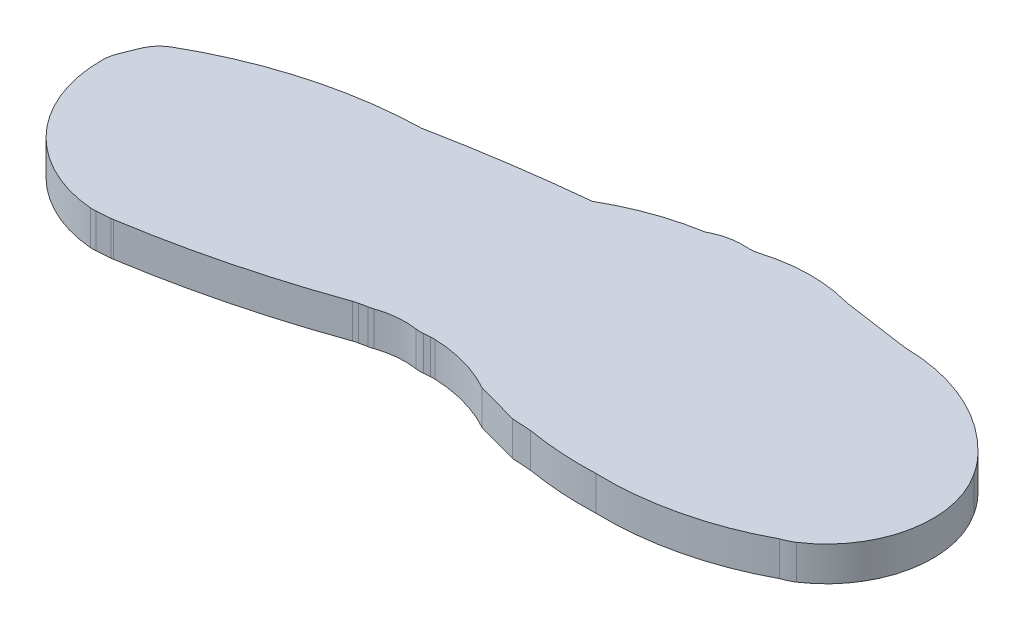
SolidWorks part; units mm, degrees
ref_plane "Front Plane" through (0, 0, 0) normal (0, 0, 1) x (1, 0, 0)
ref_plane "Top Plane" through (0, 0, 0) normal (0, 1, 0) x (1, 0, 0)
ref_plane "Right Plane" through (0, 0, 0) normal (1, 0, 0) x (0, 0, -1)
sketch "Sketch1" plane through (0, 0, 0) normal (0, 1, 0) x (1, 0, 0)
  line L0 (45.8333, 91.5) -> (229.1667, 91.5) construction
  line L9 (51.8053, 46.2547) -> (56.8676, 46.6901)
  line L12 (79.0038, 114.3802) -> (83.0543, 114.7286)
  line L14 (55.8689, 56.4332) -> (15.5662, 87.3281)
  line L15 (59.6317, 65.8579) -> (19.3289, 96.7529)
  line L16 (15.5662, 87.3281) -> (19.3289, 96.7529)
  line L19 (69.8952, 80.3749) -> (117.3677, 118.5887)
  line L21 (133.3146, 63.2727) -> (129.5681, 62.9505)
  line L23 (129.5681, 62.9505) -> (105.0351, 105.8988)
  line L25 (116.8247, 61.8545) -> (113.0574, 61.1029)
  line L26 (116.8247, 61.8545) -> (90.8367, 92.1886)
  line L27 (113.0574, 61.1029) -> (87.0695, 91.437)
  line L29 (184.4471, 132.2095) -> (204.3821, 129.3605)
  line L33 (165.1854, 54.5779) -> (153.0409, 57.8911)
  line L39 (160.5906, 102.174) -> (179.6581, 104.9064)
  line L43 (197.9816, 92.87) -> (234.0782, 63.123)
  line L46 (219.8398, 79.2449) -> (240.395, 112.1443)
  line L47 (225.5366, 74.5502) -> (246.0919, 107.4496)
  line L50 (119.3858, 87.3281) -> (144.8138, 109.1257)
  line L51 (123.3576, 80.3749) -> (148.7857, 102.1725)
  line L53 (144.8138, 109.1257) -> (147.8433, 111.9787)
  line L54 (108.6025, 106.2056) -> (107.5216, 107.9003)
  line L55 (107.5216, 107.9003) -> (115.1407, 114.0334)
  line L56 (105.0351, 105.8988) -> (90.8367, 92.1886)
  line L57 (87.0695, 91.437) -> (66.5995, 71.8536)
  line L58 (56.8676, 46.6901) -> (66.5995, 71.8536)
  line L59 (69.8952, 80.3749) -> (83.0543, 114.7286)
  line L60 (55.8689, 56.4332) -> (51.8053, 46.2547)
  line L61 (59.6317, 65.8579) -> (79.0038, 114.3802)
  line L62 (115.1407, 114.0334) -> (122.5537, 120.4385)
  line L63 (108.6025, 106.2056) -> (119.3858, 87.3281)
  line L64 (123.3576, 80.3749) -> (133.3146, 63.2727)
  line L65 (148.7857, 102.1725) -> (153.0409, 57.8911)
  line L66 (147.8433, 111.9787) -> (146.1657, 129.4371)
  line L67 (158.3087, 125.8107) -> (157.7665, 131.4276)
  line L68 (160.0972, 107.2851) -> (180.4194, 109.247)
  line L69 (158.3087, 125.8107) -> (160.0972, 107.2851)
  line L70 (160.5906, 102.174) -> (165.1854, 54.5779)
  line L71 (180.4194, 109.247) -> (184.4471, 132.2095)
  line L72 (179.6581, 104.9064) -> (170.7675, 54.2189)
  line L73 (190.9742, 52.9192) -> (197.9816, 92.87)
  line L74 (198.6541, 96.7039) -> (204.3821, 129.3605)
  line L75 (198.6541, 96.7039) -> (219.8398, 79.2449)
  line L76 (225.5366, 74.5502) -> (237.4451, 64.7364)
  line L78 (240.395, 112.1443) -> (241.2539, 113.519)
  line L79 (117.3677, 118.5887) -> (122.0886, 120.7766)
  arc A5 (241.2539, 113.519) -> (246.0919, 107.4496) centre (216.3148, 88.677) cw
  arc A6 (237.4451, 64.7364) -> (234.0782, 63.123) centre (229.0743, 77.8855) cw
  arc A7 (170.7675, 54.2189) -> (190.9742, 52.9192) centre (187.1326, 150.9211) ccw
  arc A8 (146.1657, 129.4371) -> (157.7665, 131.4276) centre (154.881, 113.4441) cw
  arc A9 (122.0886, 120.7766) -> (122.5537, 120.4385) centre (122.1521, 120.375) cw
extrude "Boss-Extrude1" add sketch "Sketch1" along normal blind 10
sketch "Sketch3" plane through (0, 0, 0) normal (0, -1, 0) x (-1, 0, 0)
  line L0 (-184.4471, 132.2095) -> (-184.0963, 130.2095)
  line L1 (-184.4471, 132.2095) -> (-180.4194, 109.247) construction
  line L2 (-157.7665, 131.4276) -> (-157.9596, 129.4276)
  line L3 (-160.0972, 107.2851) -> (-157.7665, 131.4276) construction
  arc A0 (-184.4471, 132.2095) -> (-157.7665, 131.4276) centre (-172.3516, 89.3377) cw
  arc A1 (-184.0963, 130.2095) -> (-157.9596, 129.4276) centre (-172.3013, 87.2492) cw
  dimension "D3" = 44.5453
  dimension "D4" = 44.55
  dimension "D1" = 2
  dimension "D2" = 2
extrude "Boss-Extrude2" add sketch "Sketch3" against normal blind 10
fillet "Fillet1" radius 10 1 edges at (157.7665, 5, -131.4276)
sketch "Sketch4" plane through (0, 0, 0) normal (0, -1, 0) x (1, 0, 0)
  line L0 (241.2539, -113.519) -> (240.1941, -111.8228)
  line L1 (241.2539, -113.519) -> (219.8398, -79.2449) construction
  line L2 (204.3821, -129.3605) -> (204.0366, -127.3905)
  line L3 (198.6541, -96.7039) -> (204.3821, -129.3605) construction
  arc A0 (241.2539, -113.519) -> (204.3821, -129.3605) centre (203.881, -77.3629) cw
  arc A1 (240.1941, -111.8228) -> (204.0366, -127.3905) centre (203.0818, -75.3993) cw
  dimension "D1" = 52
  dimension "D4" = 52
  dimension "D2" = 2
  dimension "D3" = 2
extrude "Boss-Extrude3" add sketch "Sketch4" against normal blind 10
fillet "Fillet2" radius 10 1 edges at (204.3821, 5, -129.3605)
fillet "Fillet3" radius 10 1 edges at (184.4471, 5, -132.2095)
sketch "Sketch5" plane through (0, 0, 0) normal (0, -1, 0) x (-1, 0, 0)
  line L0 (-146.1657, 129.4371) -> (-146.357, 127.4462)
  line L1 (-146.1657, 129.4371) -> (-147.8433, 111.9787) construction
  arc A0 (-122.0886, 120.7766) -> (-146.1657, 129.4371) centre (-158.297, 57.9116) ccw
  arc A1 (-122.0886, 120.7766) -> (-122.5537, 120.4385) centre (-122.1521, 120.375) ccw
  arc A2 (-146.357, 127.4462) -> (-122.5537, 120.4385) centre (-154.6429, 55.3709) cw
  dimension "D1" = 72.5469
  dimension "D3" = 72.55
  dimension "D2" = 2
extrude "Boss-Extrude4" add sketch "Sketch5" against normal blind 10
sketch "Sketch6" plane through (0, 0, 0) normal (0, -1, 0) x (1, 0, 0)
  line L0 (117.3677, -118.5887) -> (83.0543, -114.7286)
  line L1 (83.0543, -114.7286) -> (79.0038, -114.3802)
  line L2 (122.0886, -120.7766) -> (117.3677, -118.5887)
  arc A0 (122.0886, -120.7766) -> (79.0038, -114.3802) centre (166.68, 327.8872) cw
extrude "Boss-Extrude5" add sketch "Sketch6" against normal blind 10
sketch "Sketch7" plane through (0, 10, 0) normal (0, 1, 0) x (1, 0, 0)
  line L0 (79.0038, 114.3802) -> (78.2622, 112.5228)
  line L1 (79.0038, 114.3802) -> (59.6317, 65.8579) construction
  line L2 (19.3289, 96.7529) -> (20.9162, 95.5361)
  line L3 (59.6317, 65.8579) -> (19.3289, 96.7529) construction
  arc A0 (79.0038, 114.3802) -> (19.3289, 96.7529) centre (81.9672, -5.4758) ccw
  arc A1 (20.9162, 95.5361) -> (78.2622, 112.5228) centre (82.5636, -7.29) cw
  dimension "D2" = 119.8927
  dimension "D4" = 119.89
  dimension "D1" = 2
  dimension "D3" = 2
extrude "Boss-Extrude6" add sketch "Sketch7" against normal blind 10
sketch "Sketch8" plane through (0, 0, 0) normal (0, -1, 0) x (1, 0, 0)
  line L0 (51.8053, -46.2547) -> (52.5468, -48.1122)
  line L1 (55.8689, -56.4332) -> (51.8053, -46.2547) construction
  line L2 (15.5662, -87.3281) -> (17.1535, -86.1114)
  line L3 (15.5662, -87.3281) -> (55.8689, -56.4332) construction
  arc A0 (15.5662, -87.3281) -> (51.8053, -46.2547) centre (54.2224, -84.911) cw
  arc A1 (17.1535, -86.1114) -> (52.5468, -48.1122) centre (55.879, -86.6986) cw
  dimension "D2" = 38.7317
  dimension "D4" = 38.73
  dimension "D1" = 2
  dimension "D3" = 2
extrude "Boss-Extrude7" add sketch "Sketch8" against normal blind 10
sketch "Sketch9" plane through (0, 0, 0) normal (0, -1, 0) x (1, 0, 0)
  line L0 (56.8676, -46.6901) -> (57.589, -48.5554)
  line L1 (56.8676, -46.6901) -> (66.5995, -71.8536) construction
  line L2 (113.0574, -61.1029) -> (111.7562, -62.6218)
  line L3 (87.0695, -91.437) -> (113.0574, -61.1029) construction
  arc A0 (56.8676, -46.6901) -> (113.0574, -61.1029) centre (9.4061, -348.4601) cw
  arc A1 (111.7562, -62.6218) -> (57.589, -48.5554) centre (166.9349, 261.1906) cw
  dimension "D1" = 305.4795
  dimension "D4" = 328.48
  dimension "D2" = 2
  dimension "D3" = 2
extrude "Boss-Extrude8" add sketch "Sketch9" against normal blind 10
sketch "Sketch10" plane through (0, 0, 0) normal (0, -1, 0) x (-1, 0, 0)
  line L0 (-116.8247, 61.8545) -> (-115.5235, 63.3734)
  line L1 (-116.8247, 61.8545) -> (-90.8367, 92.1886) construction
  line L2 (-129.5681, 62.9505) -> (-128.5761, 64.6871)
  line L3 (-105.0351, 105.8988) -> (-129.5681, 62.9505) construction
  arc A0 (-116.8247, 61.8545) -> (-129.5681, 62.9505) centre (-125.1341, 39.8716) ccw
  arc A1 (-128.5761, 64.6871) -> (-115.5235, 63.3734) centre (-124.3097, 41.5777) cw
  dimension "D1" = 23.501
  dimension "D4" = 23.5
  dimension "D2" = 2
  dimension "D3" = 2
extrude "Boss-Extrude9" add sketch "Sketch10" against normal blind 10
sketch "Sketch11" plane through (0, 0, 0) normal (0, -1, 0) x (1, 0, 0)
  line L0 (153.0409, -57.8911) -> (152.8496, -59.8819)
  line L1 (148.7857, -102.1725) -> (153.0409, -57.8911) construction
  line L2 (133.3146, -63.2727) -> (123.3576, -80.3749) construction
  line L3 (133.3146, -63.2727) -> (132.3083, -65.0011)
  arc A0 (153.0409, -57.8911) -> (133.3146, -63.2727) centre (132.4798, -21.3687) cw
  arc A1 (152.8496, -59.8819) -> (132.3083, -65.0011) centre (132.7754, -23.1037) cw
  dimension "D3" = 41.9123
  dimension "D4" = 41.9
  dimension "D1" = 2
  dimension "D2" = 2
extrude "Boss-Extrude10" add sketch "Sketch11" against normal blind 10
sketch "Sketch12" plane through (0, 0, 0) normal (0, -1, 0) x (1, 0, 0)
  line L0 (170.7675, -54.2189) -> (165.1854, -54.5779)
  line L1 (165.1854, -54.5779) -> (164.9932, -56.5687)
  line L2 (165.1854, -54.5779) -> (160.5906, -102.174) construction
  line L3 (164.9932, -56.5687) -> (171.113, -56.1888)
  line L4 (179.6581, -104.9064) -> (170.7675, -54.2189) construction
  line L5 (171.113, -56.1888) -> (170.7675, -54.2189)
  dimension "D1" = 2
  dimension "D2" = 2
extrude "Boss-Extrude11" add sketch "Sketch12" against normal blind 10
sketch "Sketch13" plane through (0, 0, 0) normal (0, -1, 0) x (1, 0, 0)
  line L0 (237.4451, -64.7364) -> (235.9017, -66.0084)
  line L1 (237.4451, -64.7364) -> (225.5366, -74.5502) construction
  line L2 (225.5366, -74.5502) -> (246.0919, -107.4496) construction
  line L3 (245.0321, -105.7534) -> (246.0919, -107.4496)
  arc A0 (237.4451, -64.7364) -> (246.0919, -107.4496) centre (220.4119, -90.4164) cw
  arc A1 (235.9017, -66.0084) -> (245.0321, -105.7534) centre (219.0201, -90.8078) cw
  dimension "D3" = 30.8154
  dimension "D4" = 30
  dimension "D1" = 2
  dimension "D2" = 2
extrude "Boss-Extrude12" add sketch "Sketch13" against normal blind 10
sketch "Sketch14" plane through (0, 0, 0) normal (0, -1, 0) x (1, 0, 0)
  line L0 (190.9742, -52.9192) -> (191.3198, -54.8891)
  line L1 (190.9742, -52.9192) -> (197.9816, -92.87) construction
  line L2 (234.0782, -63.123) -> (232.5347, -64.395)
  line L3 (197.9816, -92.87) -> (234.0782, -63.123) construction
  arc A0 (234.0782, -63.123) -> (190.9742, -52.9192) centre (193.3858, -138.8751) ccw
  arc A1 (232.5347, -64.395) -> (191.3198, -54.8891) centre (193.1953, -140.8586) ccw
  dimension "D1" = 85.9897
  dimension "D2" = 85.99
  dimension "D3" = 2
  dimension "D4" = 2
extrude "Boss-Extrude13" add sketch "Sketch14" against normal blind 10
fillet "Fillet4" radius 10 4 edges at (113.0574, 5, -61.1029) (116.8247, 5, -61.8545) (133.3146, 5, -63.2727) (129.5681, 5, -62.9505)
fillet "Fillet5" radius 10 2 edges at (51.8053, 5, -46.2547) (56.8676, 5, -46.6901)
fillet "Fillet6" radius 10 2 edges at (15.5662, 5, -87.3281) (19.3289, 5, -96.7529)
sketch "Sketch15" plane through (0, 10, 0) normal (0, 1, 0) x (1, 0, 0)
  line L0 (78.2622, 112.5228) -> (59.6317, 65.8579)
  line L1 (59.6317, 65.8579) -> (20.9162, 95.5361)
  arc A0 (20.9162, 95.5361) -> (78.2622, 112.5228) centre (82.5636, -7.29) cw
extrude "Boss-Extrude14" add sketch "Sketch15" against normal blind 3
sketch "Sketch16" plane through (0, 10, 0) normal (0, 1, 0) x (1, 0, 0)
  line L0 (52.5468, 48.1122) -> (55.8689, 56.4332)
  line L1 (55.8689, 56.4332) -> (17.1535, 86.1114)
  line L2 (66.5995, 71.8536) -> (57.589, 48.5554)
  line L3 (66.5995, 71.8536) -> (87.0695, 91.437)
  line L4 (87.0695, 91.437) -> (111.7562, 62.6218)
  line L5 (115.5235, 63.3734) -> (90.8367, 92.1886)
  line L6 (90.8367, 92.1886) -> (105.0351, 105.8988)
  line L7 (105.0351, 105.8988) -> (128.5761, 64.6871)
  line L8 (132.3083, 65.0011) -> (123.3576, 80.3749)
  line L9 (123.3576, 80.3749) -> (148.7857, 102.1725)
  line L10 (148.7857, 102.1725) -> (152.8496, 59.8819)
  line L11 (117.3677, 118.5887) -> (83.0543, 114.7286)
  line L12 (83.0543, 114.7286) -> (69.8952, 80.3749)
  line L13 (69.8952, 80.3749) -> (117.3677, 118.5887)
  line L14 (122.5537, 120.4385) -> (115.1407, 114.0334)
  line L15 (115.1407, 114.0334) -> (107.5216, 107.9003)
  line L16 (107.5216, 107.9003) -> (109.1328, 105.8988)
  line L17 (109.1328, 105.8988) -> (119.3858, 87.3281)
  line L18 (119.3858, 87.3281) -> (147.8433, 111.9787)
  line L19 (147.8433, 111.9787) -> (146.357, 127.4462)
  line L20 (179.6581, 104.9064) -> (160.5906, 102.174)
  line L21 (160.5906, 102.174) -> (164.9932, 56.5687)
  line L22 (164.9932, 56.5687) -> (171.113, 56.1888)
  line L23 (171.113, 56.1888) -> (179.6581, 104.9064)
  line L24 (180.4194, 109.247) -> (184.0963, 130.2095)
  line L25 (157.9596, 129.4276) -> (160.0972, 107.2851)
  line L26 (160.0972, 107.2851) -> (180.4194, 109.247)
  line L27 (197.9816, 92.87) -> (191.3198, 54.8891)
  line L28 (197.9816, 92.87) -> (232.5347, 64.395)
  line L29 (240.1941, 111.8228) -> (219.8398, 79.2449)
  line L30 (219.8398, 79.2449) -> (198.6541, 96.7039)
  line L31 (198.6541, 96.7039) -> (204.0366, 127.3905)
  line L32 (235.9017, 66.0084) -> (225.5366, 74.5502)
  line L33 (225.5366, 74.5502) -> (245.0321, 105.7534)
  arc A0 (17.1535, 86.1114) -> (52.5468, 48.1122) centre (55.879, 86.6986) ccw
  arc A1 (57.589, 48.5554) -> (111.7562, 62.6218) centre (166.9349, -261.1906) cw
  arc A2 (115.5235, 63.3734) -> (128.5761, 64.6871) centre (124.3097, 41.5777) cw
  arc A3 (132.3083, 65.0011) -> (152.8496, 59.8819) centre (132.7754, 23.1037) cw
  arc A4 (122.5537, 120.4385) -> (146.357, 127.4462) centre (154.6429, 55.3709) cw
  arc A5 (184.0963, 130.2095) -> (157.9596, 129.4276) centre (172.3013, 87.2492) ccw
  arc A6 (191.3198, 54.8891) -> (232.5347, 64.395) centre (193.1953, 140.8586) ccw
  arc A7 (204.0366, 127.3905) -> (240.1941, 111.8228) centre (203.0818, 75.3993) cw
  arc A8 (245.0321, 105.7534) -> (235.9017, 66.0084) centre (219.0201, 90.8078) cw
extrude "Boss-Extrude16" add sketch "Sketch16" against normal blind 3 contours L1 A0 L0
sketch "Sketch20" plane through (0, 10, 0) normal (0, 1, 0) x (1, 0, 0)
  line L0 (57.589, 48.5554) -> (66.5995, 71.8536)
  line L1 (66.5995, 71.8536) -> (87.0695, 91.437)
  line L2 (87.0695, 91.437) -> (111.7562, 62.6218)
  arc A0 (111.7562, 62.6218) -> (57.589, 48.5554) centre (166.9349, -261.1906) ccw
extrude "Boss-Extrude17" add sketch "Sketch20" against normal blind 3
sketch "Sketch21" plane through (0, 10, 0) normal (0, 1, 0) x (1, 0, 0)
  line L0 (69.8952, 80.3749) -> (83.0543, 114.7286)
  line L1 (83.0543, 114.7286) -> (117.3677, 118.5887)
  line L2 (117.3677, 118.5887) -> (69.8952, 80.3749)
extrude "Boss-Extrude18" add sketch "Sketch21" against normal blind 3
sketch "Sketch22" plane through (0, 10, 0) normal (0, 1, 0) x (1, 0, 0)
  line L0 (115.5235, 63.3734) -> (90.8367, 92.1886)
  line L1 (90.8367, 92.1886) -> (105.0351, 105.8988)
  line L2 (105.0351, 105.8988) -> (128.5761, 64.6871)
  arc A0 (115.5235, 63.3734) -> (128.5761, 64.6871) centre (124.3097, 41.5777) cw
extrude "Boss-Extrude19" add sketch "Sketch22" against normal blind 3
sketch "Sketch23" plane through (0, 10, 0) normal (0, 1, 0) x (1, 0, 0)
  line L0 (152.8496, 59.8819) -> (148.7857, 102.1725)
  line L1 (148.7857, 102.1725) -> (123.3576, 80.3749)
  line L2 (123.3576, 80.3749) -> (132.3083, 65.0011)
  arc A0 (132.3083, 65.0011) -> (152.8496, 59.8819) centre (132.7754, 23.1037) cw
extrude "Boss-Extrude20" add sketch "Sketch23" against normal blind 3
sketch "Sketch24" plane through (0, 10, 0) normal (0, 1, 0) x (1, 0, 0)
  line L0 (107.5216, 107.9003) -> (108.6025, 106.2056)
  line L1 (108.6025, 106.2056) -> (119.3858, 87.3281)
  line L2 (119.3858, 87.3281) -> (147.8433, 111.9787)
  line L3 (147.8433, 111.9787) -> (146.357, 127.4462)
  line L4 (122.5537, 120.4385) -> (115.1407, 114.0334)
  line L5 (115.1407, 114.0334) -> (107.5216, 107.9003)
  arc A0 (122.5537, 120.4385) -> (146.357, 127.4462) centre (154.6429, 55.3709) cw
extrude "Boss-Extrude21" add sketch "Sketch24" against normal blind 3
sketch "Sketch25" plane through (0, 10, 0) normal (0, 1, 0) x (1, 0, 0)
  line L0 (157.9596, 129.4276) -> (160.0972, 107.2851)
  line L1 (160.0972, 107.2851) -> (180.4194, 109.247)
  line L2 (180.4194, 109.247) -> (184.0963, 130.2095)
  arc A0 (157.9596, 129.4276) -> (184.0963, 130.2095) centre (172.3013, 87.2492) cw
extrude "Boss-Extrude22" add sketch "Sketch25" against normal blind 3
sketch "Sketch26" plane through (0, 10, 0) normal (0, 1, 0) x (1, 0, 0)
  line L0 (160.5906, 102.174) -> (164.9932, 56.5687)
  line L1 (164.9932, 56.5687) -> (171.113, 56.1888)
  line L2 (171.113, 56.1888) -> (179.6581, 104.9064)
  line L3 (179.6581, 104.9064) -> (160.5906, 102.174)
extrude "Boss-Extrude23" add sketch "Sketch26" against normal blind 3
sketch "Sketch27" plane through (0, 10, 0) normal (0, 1, 0) x (1, 0, 0)
  line L0 (119.3858, 87.3281) -> (144.8138, 109.1257)
  line L1 (144.8138, 109.1257) -> (147.8433, 111.9787)
  line L2 (147.8433, 111.9787) -> (119.3858, 87.3281)
extrude "Boss-Extrude24" add sketch "Sketch27" against normal blind 3
sketch "Sketch28" plane through (0, 10, 0) normal (0, 1, 0) x (1, 0, 0)
  line L0 (235.9017, 66.0084) -> (225.5366, 74.5502)
  line L1 (225.5366, 74.5502) -> (245.0321, 105.7534)
  arc A0 (245.0321, 105.7534) -> (235.9017, 66.0084) centre (219.0201, 90.8078) cw
extrude "Boss-Extrude25" add sketch "Sketch28" against normal blind 3
sketch "Sketch29" plane through (0, 10, 0) normal (0, 1, 0) x (1, 0, 0)
  line L0 (191.3198, 54.8891) -> (197.9816, 92.87)
  line L1 (197.9816, 92.87) -> (232.5347, 64.395)
  arc A0 (232.5347, 64.395) -> (191.3198, 54.8891) centre (193.1953, 140.8586) cw
extrude "Boss-Extrude26" add sketch "Sketch29" against normal blind 3
sketch "Sketch30" plane through (0, 10, 0) normal (0, 1, 0) x (1, 0, 0)
  line L0 (204.0366, 127.3905) -> (198.6541, 96.7039)
  line L1 (198.6541, 96.7039) -> (219.8398, 79.2449)
  line L2 (219.8398, 79.2449) -> (240.1941, 111.8228)
  arc A0 (204.0366, 127.3905) -> (240.1941, 111.8228) centre (203.0818, 75.3993) cw
extrude "Boss-Extrude27" add sketch "Sketch30" against normal blind 3
sketch "Sketch31" plane through (0, 0, 0) normal (0, -1, 0) x (-1, 0, 0)
  line L0 (-122.0886, 120.7766) -> (-120.1859, 128.0668) construction
